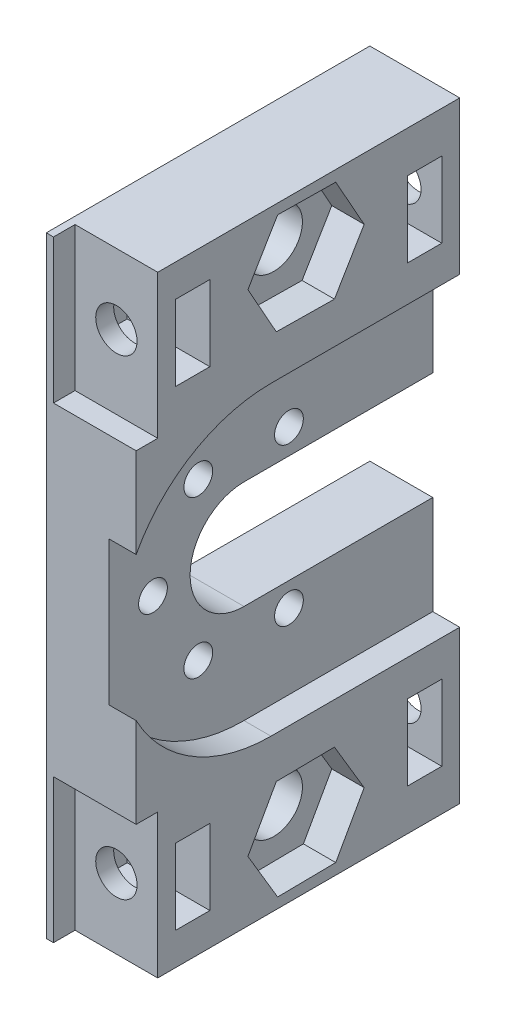
SolidWorks part; units mm, degrees
ref_plane "正面" through (0, 0, 0) normal (1, 0, 0) x (0, 1, 0)
ref_plane "平面" through (0, 0, 0) normal (0, 0, 1) x (0, 1, 0)
ref_plane "右側面" through (0, 0, 0) normal (0, 1, 0) x (-1, 0, 0)
sketch "ｽｹｯﾁ1" plane through (0, 0, 0) normal (1, 0, 0) x (0, 1, 0)
  line L0 (3, 0) -> (3, -10.5)
  line L1 (0, 5) -> (-4.3301, 2.5) construction
  line L2 (-4.3301, 2.5) -> (-4.3301, -2.5) construction
  line L3 (-4.3301, -2.5) -> (0, -5) construction
  line L4 (0, -5) -> (4.3301, -2.5) construction
  line L5 (4.3301, -2.5) -> (4.3301, 2.5) construction
  line L6 (4.3301, 2.5) -> (0, 5) construction
  line L7 (-17, 7.5) -> (17, 7.5)
  line L8 (-17, 7.5) -> (-17, -10.5)
  line L9 (-17, -10.5) -> (17, -10.5)
  line L10 (17, 7.5) -> (17, -10.5)
  line L11 (3, -10.5) -> (-3, -10.5)
  line L12 (-3, -10.5) -> (-3, 0)
  line L13 (-3, 0) -> (3, 0)
  circle A0 centre (0, 0) radius 0.75
  circle A1 centre (0, 0) radius 3
  circle A2 centre (0, 0) radius 4.3301 construction
  circle A3 centre (-4.3301, -2.5) radius 0.8
  circle A4 centre (-4.3301, 2.5428) radius 0.8
  circle A5 centre (0.0371, 5.0642) radius 0.8
  circle A6 centre (4.4043, 2.5428) radius 0.8
  circle A7 centre (4.4043, -2.5) radius 0.8
  circle A8 centre (0.0371, -5.0214) radius 0.8
  circle A9 centre (0, 0) radius 8.5
  point P25 (0.0371, 0.0214)
  dimension "D1" = 1.5
  dimension "D2" = 6
  dimension "D3" = 10
  dimension "D4" = 1.6
  dimension "D6" = 17
  dimension "D7" = 10.5
  dimension "D8" = 18
  dimension "D9" = 17
  dimension "D10" = 34
  dimension "D5" = 6
extrude "ﾎﾞｽ - 押し出し5" add sketch "ｽｹｯﾁ1" against normal blind 5 contours A9 L7 L8 L9 L12 | L0 A9 L7 L12 A1 A7 A6 A5 A4 A3 | A9 L0 L9 L10 L7 region at (0, 0, 3.2297) region at (0, 11.5835, -1.9938) region at (0, -11.5835, -1.9938)
sketch "ｽｹｯﾁ6" plane through (0, 0, 0) normal (1, 0, 0) x (0, 1, 0)
  line L0 (-8.5, 0) -> (-8.5, -10.5)
  line L1 (-17, -10.5) -> (-3, -10.5) construction
  line L2 (-8.5, -10.5) -> (8.5, -10.5)
  line L3 (3, -10.5) -> (17, -10.5) construction
  line L4 (8.5, -10.5) -> (8.5, 0)
  line L5 (8.5, 0) -> (-8.5, 0)
  circle A0 centre (0, 0) radius 8.5
  line M1 (-3, -10.5) -> (-3, 0)
  arc M2 (-3, 0) -> (3, 0) centre (0, 0) cw
  line M3 (3, 0) -> (3, -10.5)
  line M4 (3, -10.5) -> (17, -10.5)
  line M6 (17, 7.5) -> (-17, 7.5)
  line M8 (-17, -10.5) -> (-3, -10.5)
  circle M9 centre (4.4043, -2.5) radius 0.8
  circle M10 centre (4.4043, 2.5428) radius 0.8
  circle M11 centre (0.0371, 5.0642) radius 0.8
  circle M12 centre (-4.3301, 2.5428) radius 0.8
  circle M13 centre (-4.3301, -2.5) radius 0.8
  dimension "D1" = 17
extrude "ｶｯﾄ - 押し出し1" cut sketch "ｽｹｯﾁ6" against normal blind 1.5 contours L5 A0 M6 M2 M11 M12 M10 | L5 A0 M1 M13 | A0 L5 M3 M9 | A0 L4 M3 M4 | A0 L0 M8 M1 region at (0, -6.331, -7.7933) region at (0, -0.0025, 3.7345) region at (0, -5.3392, -3.2178) region at (0, 5.3342, -3.2178) region at (0, 6.331, -7.7933)
sketch "ｽｹｯﾁ7" plane through (-5, 0, 0) normal (-1, 0, 0) x (0, -1, 0)
  line L0 (0, 0) -> (0, 8.5494) construction
  line L1 (17, -10.5) -> (3, -10.5) construction
  line L2 (5.0623, -10.5) -> (-7.5408, -10.5) construction
  line L3 (5.0623, -10.5) -> (5.0623, -11.7) construction
  line L4 (5.0623, -11.7) -> (-7.5408, -11.7) construction
  line L5 (-7.5408, -10.5) -> (-7.5408, -11.7) construction
  line L6 (4.5077, -13.7) -> (2.1261, -13.7) construction
  circle A0 centre (0, 0) radius 3.25 construction
  circle A1 centre (-13.611, -1.95) radius 10.5 construction
  circle A3 centre (-13.611, -1.95) radius 11.75 construction
  circle A4 centre (0, 0) radius 8.5 construction
  circle A5 centre (-13.611, -1.95) radius 1.6
  circle A6 centre (13.611, -1.95) radius 1.6
  dimension "D1" = 6.5
  dimension "D2" = 21
  dimension "D3" = 23.5
  dimension "D4" = 17
  dimension "D5" = 1.2
  dimension "D6" = 10.5
  dimension "D8" = 3.2
  dimension "D7" = 2
extrude "ｶｯﾄ - 押し出し2" cut sketch "ｽｹｯﾁ7" against normal through all contours A6 | A5
sketch "ｽｹｯﾁ8" plane through (0, 0, 0) normal (1, 0, 0) x (0, 1, 0)
  line L0 (0, 0) -> (0, -2.816) construction
  line L13 (10.7903, -3.5301) -> (10.8322, -0.2972)
  line L14 (-10.8322, -0.2972) -> (-13.653, 1.2829)
  line L15 (-13.653, 1.2829) -> (-16.4318, -0.3699)
  line L16 (-16.4318, -0.3699) -> (-16.3898, -3.6028)
  line L17 (-16.3898, -3.6028) -> (-13.5691, -5.1829)
  line L18 (-13.5691, -5.1829) -> (-10.7903, -3.5301)
  line L19 (-10.7903, -3.5301) -> (-10.8322, -0.2972)
  line L20 (13.5691, -5.1829) -> (10.7903, -3.5301)
  line L21 (16.3898, -3.6028) -> (13.5691, -5.1829)
  line L22 (16.4318, -0.3699) -> (16.3898, -3.6028)
  line L23 (13.653, 1.2829) -> (16.4318, -0.3699)
  line L24 (10.8322, -0.2972) -> (13.653, 1.2829)
  circle A0 centre (-13.611, -1.95) radius 3.2332 construction
  dimension "D1" = 5.6
extrude "ｶｯﾄ - 押し出し4" cut sketch "ｽｹｯﾁ8" against normal blind 1.8
sketch "ｽｹｯﾁ9" plane through (0, 0, -10.5) normal (0, 0, -1) x (1, 0, 0)
  line L0 (0, 17) -> (0, 8.5) construction
  line L1 (0, 12.5081) -> (-1.15, 14.5) construction
  line L2 (-1.15, 14.5) -> (-3.45, 14.5) construction
  line L3 (-3.45, 14.5) -> (-4.6, 12.5081) construction
  line L4 (-4.6, 12.5081) -> (-3.45, 10.5163) construction
  line L5 (-3.45, 10.5163) -> (-1.15, 10.5163) construction
  line L6 (-1.15, 10.5163) -> (0, 12.5081) construction
  line L8 (-5, 17) -> (0, 17) construction
  line L9 (-1.5, 8.5) -> (0, 8.5) construction
  line L10 (0, 0) -> (-7.4741, 0) construction
  circle A0 centre (-2.3, 12.5081) radius 1.9919 construction
  circle A1 centre (-2.3, 12.5081) radius 1.15
  circle A2 centre (-2.3, -12.5081) radius 1.15
  dimension "D2" = 2.3
  dimension "D1" = 4.6
  dimension "D3" = 2.5
  dimension "D4" = 2.0163
  dimension "D5" = 4.4919
extrude "ｶｯﾄ - 押し出し5" cut sketch "ｽｹｯﾁ9" against normal blind 1
sketch "ｽｹｯﾁ10" plane through (0, 0, 0) normal (1, 0, 0) x (0, 1, 0)
  line L0 (-17, 7.5) -> (-17, -10.5) construction
  line L1 (-14.7, -7.6) -> (-10.5, -7.6)
  line L2 (-14.7, -7.6) -> (-14.7, -9.5)
  line L3 (-14.7, -9.5) -> (-10.5, -9.5)
  line L4 (-10.5, -7.6) -> (-10.5, -9.5)
  line L5 (-17, -10.5) -> (-8.5, -10.5) construction
  line L6 (0, 0) -> (0, -3.2904) construction
  line L7 (14.7, -9.5) -> (10.5, -9.5)
  line L8 (10.5, -7.6) -> (10.5, -9.5)
  line L9 (14.7, -7.6) -> (10.5, -7.6)
  line L10 (14.7, -7.6) -> (14.7, -9.5)
  line L11 (-17, -1.5) -> (0.4912, -1.5) construction
  line L12 (-15.2, 5.3) -> (-11, 5.3)
  line L13 (-15.2, 5.3) -> (-15.2, 3.4)
  line L14 (-15.2, 3.4) -> (-11, 3.4)
  line L15 (-11, 5.3) -> (-11, 3.4)
  line L16 (15.2, 5.3) -> (15.2, 3.4)
  line L17 (-17, 7.5) -> (-9, 7.5)
  line L18 (-17, 7.5) -> (-17, 6.3)
  line L19 (-17, 6.3) -> (-9, 6.3)
  line L20 (-9, 7.5) -> (-9, 6.3)
  line L21 (15.2, 3.4) -> (11, 3.4)
  line L22 (11, 5.3) -> (11, 3.4)
  line L23 (15.2, 5.3) -> (11, 5.3)
  line L24 (17, 6.3) -> (9, 6.3)
  line L25 (9, 7.5) -> (9, 6.3)
  line L26 (17, 7.5) -> (9, 7.5)
  line L27 (17, 7.5) -> (17, 6.3)
  dimension "D1" = 2.3
  dimension "D2" = 4.2
  dimension "D3" = 1
  dimension "D4" = 1.9
  dimension "D5" = 4.2
  dimension "D6" = 1.9
  dimension "D7" = 1.8
  dimension "D8" = 1
  dimension "D9" = 1.2
  dimension "D10" = 8
extrude "ｶｯﾄ - 押し出し6" cut sketch "ｽｹｯﾁ10" against normal blind 4.6
sketch "ｽｹｯﾁ11" plane through (-5, 0, 0) normal (-1, 0, 0) x (0, -1, 0)
  line L0 (-16.0545, -10.5) -> (-24.2013, -10.5) construction
  line L2 (0, 0) -> (0, -13.1079) construction
  line L3 (-22.0311, -10.5) -> (22.0311, -10.5) construction
  line L4 (-22.0311, -10.5) -> (-22.0311, -11.7) construction
  line L5 (-22.0311, -11.7) -> (22.0311, -11.7) construction
  line L6 (22.0311, -10.5) -> (22.0311, -11.7) construction
  circle A0 centre (-13.611, -1.95) radius 12 construction
  circle A1 centre (13.611, -1.95) radius 12 construction
  dimension "D1" = 24
  dimension "D2" = 1.2
  dimension "D3" = 44.0622
sketch "ｽｹｯﾁ12" plane through (0, 0, 5.3) normal (0, 0, -1) x (1, 0, 0)
  line L1 (0, 11) -> (0, 15.2) construction
  line L2 (0, 0) -> (-5.9641, 0) construction
  line L3 (0, 13.1) -> (-1.15, 15.0919) construction
  line L4 (-1.15, 15.0919) -> (-3.45, 15.0919) construction
  line L5 (-3.45, 15.0919) -> (-4.6, 13.1) construction
  line L6 (-4.6, 13.1) -> (-3.45, 11.1081) construction
  line L7 (-3.45, 11.1081) -> (-1.15, 11.1081) construction
  line L8 (-1.15, 11.1081) -> (0, 13.1) construction
  circle A4 centre (-2.3, 13.1) radius 1.9919 construction
  circle A5 centre (-2.3, 13.1) radius 1.15
  circle A6 centre (-2.3, -13.1) radius 1.15
  dimension "D1" = 4.6
  dimension "D2" = 2.3
extrude "ｶｯﾄ - 押し出し7" cut sketch "ｽｹｯﾁ12" against normal through all contours A5 | A6
